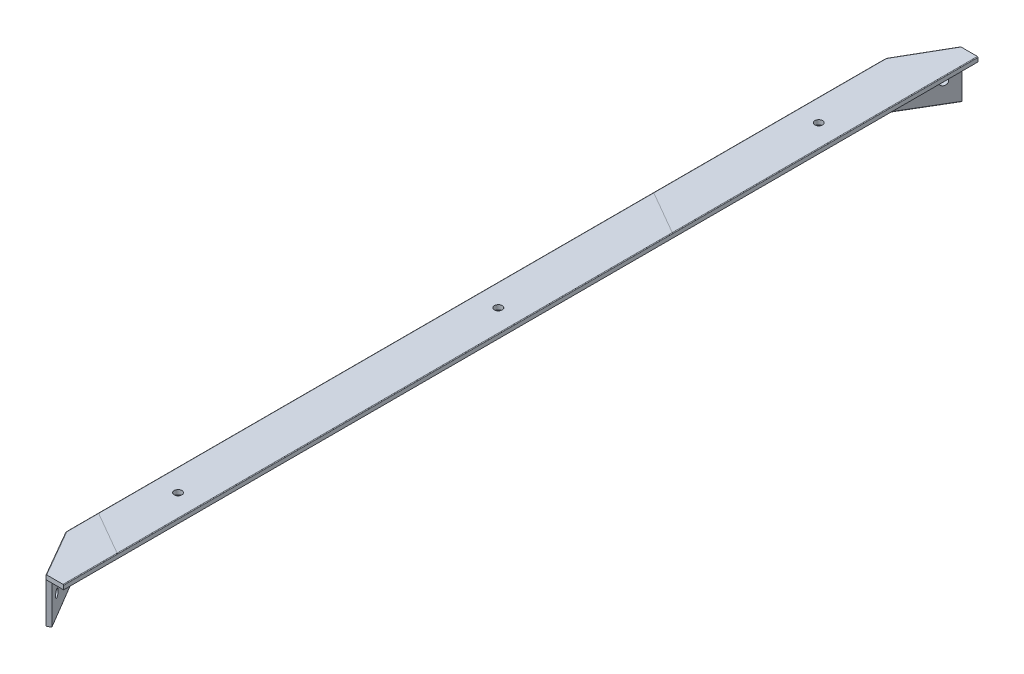
SolidWorks part; units mm, degrees
material "1.0116 (S235J2G3)"
ref_plane "Front Plane" through (0, 0, 0) normal (0, 0, 1) x (1, 0, 0)
ref_plane "Top Plane" through (0, 0, 0) normal (0, 1, 0) x (1, 0, 0)
ref_plane "Right Plane" through (0, 0, 0) normal (1, 0, 0) x (0, 0, -1)
sketch "Sketch1" plane through (0, 0, 0) normal (0, 0, 1) x (1, 0, 0)
  line L6 (0, 0) -> (0, 70)
  line L7 (0, 70) -> (70, 70)
  line L8 (70, 70) -> (70, 63)
  line L9 (70, 63) -> (7, 63)
  line L10 (7, 63) -> (7, 0)
  line L11 (7, 0) -> (0, 0)
  dimension "D1" = 70
  dimension "D2" = 70
  dimension "D3" = 7
  dimension "D4" = 7
extrude "Boss-Extrude1" add sketch "Sketch1" along normal blind 640
sketch "Sketch21" plane through (0, 0, 0) normal (0, 0, -1) x (-1, 0, 0)
  line L0 (0, 70) -> (-70, 70) construction
  line L1 (-70, 70) -> (-70, 0) construction
  line L2 (-70, 0) -> (0, 0) construction
  line L3 (0, 0) -> (0, 69.2595) construction
sketch "Sketch22" plane through (0, 70, 0) normal (0, 1, 0) x (1, 0, 0)
  line L0 (70, 0) -> (0, 0) construction
  line L1 (0, -55) -> (0, 55) construction
  circle A0 centre (35, 0) radius 6
  circle A1 centre (35, 500) radius 6
  circle A2 centre (35, -500) radius 6
  dimension "D1" = 12
  dimension "D2" = 12
  dimension "D3" = 12
  dimension "D4" = 500
  dimension "D5" = 500
  dimension "D6" = 35
  dimension "D7" = 35
extrude "Cut-Extrude4" cut sketch "Sketch22" against normal blind 10
sketch "Sketch23" plane through (0, 0, 0) normal (0, 1, 0) x (1, 0, 0)
  line L0 (0, -640) -> (42.5, -713.6122)
  line L1 (42.5, -713.6122) -> (48.5622, -710.1122)
  line L2 (48.5622, -710.1122) -> (7, -640)
  line L3 (7, -640) -> (0, -640)
  line L4 (0, -55) -> (0, 55) construction
  dimension "D1" = 7
  dimension "D2" = 210
  dimension "D3" = 85
extrude "Boss-Extrude2" add sketch "Sketch23" along normal blind 63
sketch "Sketch25" plane through (0, 63, 0) normal (0, 1, 0) x (1, 0, 0)
  line L0 (70, -640) -> (0, -640)
  line L1 (70, -640) -> (70, 0) construction
  line L2 (7, -640) -> (70, -640) construction
  line L3 (0, -640) -> (42.5, -713.6122) construction
  line L4 (0, -640) -> (42.5, -713.6122)
  line L5 (42.5, -713.6122) -> (48.5622, -710.1122) construction
  line L6 (42.5, -713.6122) -> (70, -713.6122)
  line L7 (70, -713.6122) -> (70, -640)
extrude "Boss-Extrude3" add sketch "Sketch25" along normal blind 7
sketch "Sketch26" plane through (-275.5567, 0, 163.3488) normal (0.8602, 0, -0.5099) x (-0.5099, 0, -0.8602)
  line L0 (-635.6125, 0) -> (-554.1071, 0) construction
  line L1 (-635.6125, 63) -> (-635.6125, 0) construction
  line L2 (-554.1071, 0) -> (-554.1071, 63) construction
  circle A0 centre (-614.3625, 31.5) radius 6
  circle A1 centre (-575.3671, 31.5) radius 6
  dimension "D1" = 12
  dimension "D2" = 12
  dimension "D3" = 31.5
  dimension "D4" = 31.5
  dimension "D5" = 21.25
  dimension "D6" = 21.26
extrude "Cut-Extrude5" cut sketch "Sketch26" against normal blind 7
mirror "Mirror1" about plane through (0, 0, 0) normal (0, 0, 1) of bodies 114 116
fillet "Fillet1" radius 10 2 edges at (0, 35, -640) (0, 35, 640)
fillet "Fillet2" radius 10 2 edges at (7, 31.5, 640) (7, 31.5, -640)
sketch "Sketch27" plane through (0, 70, 0) normal (0, 1, 0) x (1, 0, 0)
  line L0 (0, -589.3476) -> (70, -629.7622)
  line L1 (0, -38.5) -> (0, 38.5) construction
  line L2 (70, -713.6122) -> (70, 713.6122) construction
  line L3 (70, -629.7622) -> (70, 236.7622)
  line L4 (70, 236.7622) -> (0, 277.1767)
  line L5 (0, 277.1767) -> (0, -589.3476)
  line L6 (42.5, -713.6122) -> (70, -713.6122) construction
  dimension "D1" = 60
  dimension "D2" = 60
  dimension "D3" = 83.85
  dimension "D4" = 476.85
split line "Split Line1"
fillet "Fillet3" radius 5 5 edges at (28.48, 63, 676.2351) (7.3558, 63, 639.9025) (28.48, 63, -676.2351) (7.3558, 63, -639.9025) (7, 63, 0)
fillet "Fillet5" radius 1 20 edges at (21.9199, 0, 677.9663) (0.3407, 0, 639.9087) (21.9199, 0, -677.9663) (0.3407, 0, -639.9087) (28.48, 0, 676.2351) (7.3558, 0, 639.9025) (28.48, 0, -676.2351) (7.3558, 0, -639.9025) (70, 70, 671.6872) (70, 70, -475.1872) (70, 70, 196.5) (21.9199, 70, 677.9663) (0.3407, 70, 639.9087) (0, 70, 613.3341) (0, 70, 156.0855) (0, 70, -457.2486) (21.9199, 70, -677.9663) (0.3407, 70, -639.9087) (0, 0, 0) (7, 0, 0)
